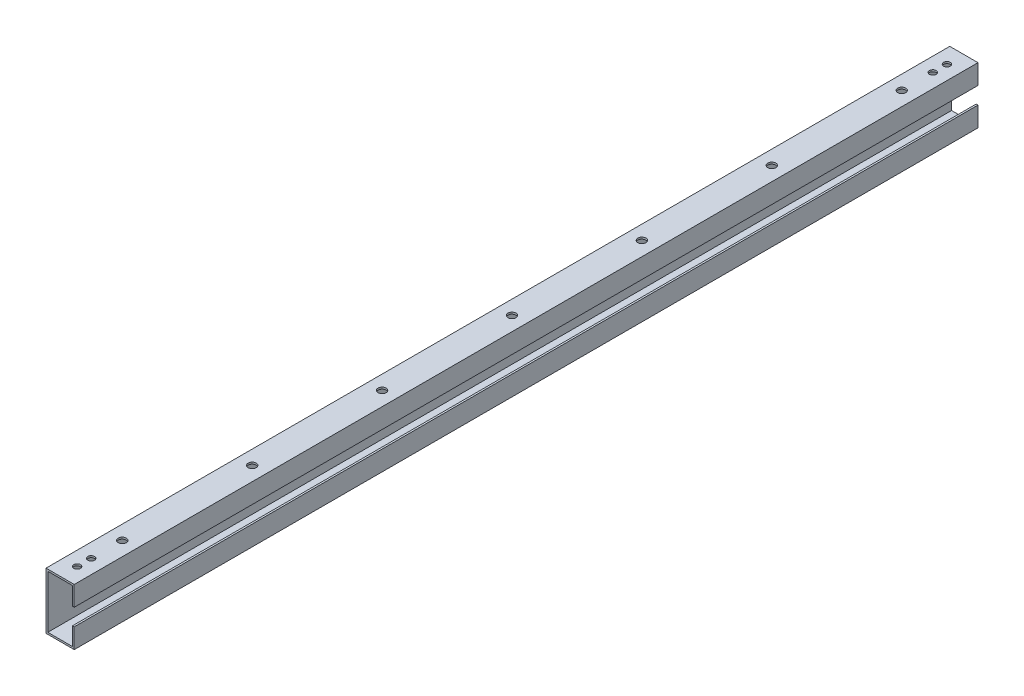
SolidWorks part; units mm, degrees
material "AISI 1020 Acero laminado en frío"
ref_plane "Alzado" through (0, 0, 0) normal (0, 0, 1) x (1, 0, 0)
ref_plane "Planta" through (0, 0, 0) normal (0, 1, 0) x (1, 0, 0)
ref_plane "Vista lateral" through (0, 0, 0) normal (1, 0, 0) x (0, 0, -1)
sketch "Croquis1" plane through (0, 0, 0) normal (0, 0, 1) x (1, 0, 0)
  line L0 (-21.825, -46.825) -> (-21.825, 46.825)
  line L1 (-25, -50) -> (25, -50)
  line L2 (-25, -50) -> (-25, 50)
  line L3 (-25, 50) -> (25, 50)
  line L4 (25, -50) -> (25, 50)
  line L5 (-25, -50) -> (25, 50) construction
  line L6 (-25, 50) -> (25, -50) construction
  line L7 (-21.825, 46.825) -> (21.825, 46.825)
  line L8 (21.825, -46.825) -> (21.825, 46.825)
  line L9 (-21.825, -46.825) -> (21.825, -46.825)
  point P0 (0, 0)
  dimension "D1" = 100
  dimension "D2" = 50
  dimension "D3" = 3.175
extrude "Saliente-Extruir1" add sketch "Croquis1" along normal mid plane 1600
sketch "Croquis2" plane through (25, 0, 0) normal (1, 0, 0) x (0, 0, -1)
  line L1 (800, 15) -> (-800, 15)
  line L2 (800, 15) -> (800, -15)
  line L3 (800, -15) -> (-800, -15)
  line L4 (-800, 15) -> (-800, -15)
  line L5 (800, 15) -> (-800, -15) construction
  line L6 (800, -15) -> (-800, 15) construction
  point P0 (0, 0)
  dimension "D1" = 1600
  dimension "D2" = 30
extrude "Cortar-Extruir1" cut sketch "Croquis2" against normal blind 5
sketch "Croquis8" plane through (25, 50, 0) normal (0, -1, 0) x (0, 0, 1)
  line L0 (850.2048, 25) -> (-1024.1629, 25) construction
  line L1 (0, 25) -> (230, 25) construction
  line L2 (0, 25) -> (-230, 25) construction
  circle A0 centre (0, 25) radius 7.1437
  circle A1 centre (230, 25) radius 7.1438
  circle A2 centre (460, 25) radius 7.1437
  circle A3 centre (690, 25) radius 7.1437
  circle A4 centre (920, 25) radius 7.1437
  circle A5 centre (1150, 25) radius 7.1437
  circle A6 centre (1380, 25) radius 7.1437
  circle A7 centre (1610, 25) radius 7.1437
  circle A8 centre (-230, 25) radius 7.1438
  circle A9 centre (-460, 25) radius 7.1438
  circle A10 centre (-690, 25) radius 7.1437
  circle A11 centre (-920, 25) radius 7.1437
  circle A12 centre (-1150, 25) radius 7.1437
  circle A13 centre (-1380, 25) radius 7.1437
  circle A14 centre (-1610, 25) radius 7.1437
  dimension "D1" = 14.2875
  dimension "D3" = 230
  dimension "D5" = 230
  dimension "D2" = 8
  dimension "D4" = 8
extrude "Cortar-Extruir2" cut sketch "Croquis8" along normal blind 130
hole_wizard "Taladro de margen para 7/161" positions "Croquis9" profile "Croquis10" hole size "7/16" standard "Ansi Inch"
sketch "Croquis9" plane through (352.4117, -54.7625, 29.7412) normal (0, -1, 0) x (-1, 0, 0)
  point P0 (-597.5883, 774.7412)
  point P3 (-597.5883, 799.7412)
  point P6 (352.4117, 799.7412)
  point P9 (352.4117, 774.7412)
sketch "Croquis10" plane through (950, -54.7625, -745) normal (1, 0, 0) x (0, 0, -1)
  line L0 (0, 0) -> (0, 155.0766)
  line L1 (0, 155.0766) -> (5.9525, 151.5)
  line L2 (5.9525, 151.5) -> (5.9525, 0)
  line L3 (5.9525, 0) -> (0, 0)
  line L4 (0, 155.0766) -> (-5.9525, 151.5) construction
  line L5 (0, -6.35) -> (0, 107.95) construction
  dimension "Diámetro de taladro" = 11.905
  dimension "Profundidad de taladro" = 151.5
  dimension "Ángulo de perforador" = 118
hole_wizard "Taladro de margen para 7/162" positions "Croquis11" profile "Croquis12" hole size "7/16" standard "Ansi Inch"
sketch "Croquis11" plane through (597.5883, -54.7625, -29.7412) normal (0, -1, 0) x (1, 0, 0)
  point P0 (-597.5883, 774.7412)
  point P3 (-597.5883, 799.7412)
  point P6 (352.4117, 799.7412)
  point P9 (352.4117, 774.7412)
sketch "Croquis12" plane through (0, -54.7625, 745) normal (1, 0, 0) x (0, 0, -1)
  line L0 (0, 0) -> (0, 155.0766)
  line L1 (0, 155.0766) -> (5.9525, 151.5)
  line L2 (5.9525, 151.5) -> (5.9525, 0)
  line L3 (5.9525, 0) -> (0, 0)
  line L4 (0, 155.0766) -> (-5.9525, 151.5) construction
  line L5 (0, -6.35) -> (0, 107.95) construction
  dimension "Diámetro de taladro" = 11.905
  dimension "Profundidad de taladro" = 151.5
  dimension "Ángulo de perforador" = 118
